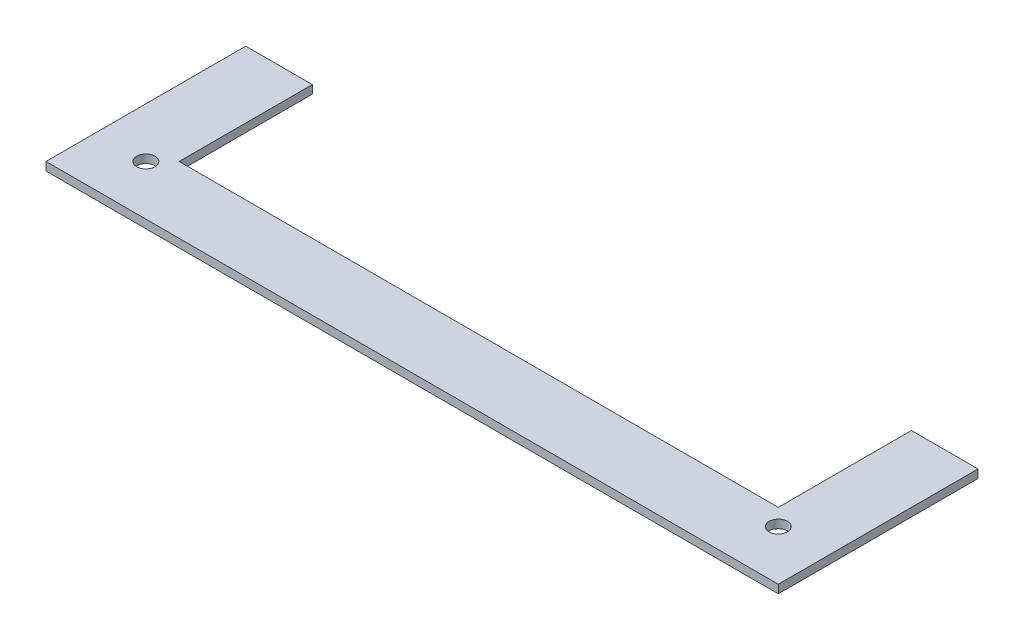
SolidWorks part; units mm, degrees
ref_plane "Front Plane" through (0, 0, 0) normal (0, 0, 1) x (1, 0, 0)
ref_plane "Top Plane" through (0, 0, 0) normal (0, 1, 0) x (1, 0, 0)
ref_plane "Right Plane" through (0, 0, 0) normal (1, 0, 0) x (0, 0, -1)
sketch "Sketch1" plane through (0, 0, 0) normal (0, 1, 0) x (1, 0, 0)
  line L0 (-139.7, 63.5) -> (-114.3, 63.5)
  line L1 (-114.3, 63.5) -> (-114.3, 12.7)
  line L2 (-114.3, 12.7) -> (114.3, 12.7)
  line L3 (114.3, 12.7) -> (114.3, 63.5)
  line L4 (114.3, 63.5) -> (139.7, 63.5)
  line L5 (139.7, 63.5) -> (139.7, -12.7)
  line L6 (139.7, -12.7) -> (-139.7, -12.7)
  line L7 (-139.7, -12.7) -> (-139.7, 63.5)
  line L8 (0, 12.7) -> (0, -12.7) construction
  line L9 (-114.3, 12.7) -> (-114.3, 6.35) construction
  line L10 (-114.3, 6.35) -> (-120.65, 6.35) construction
  line L11 (114.3, 12.7) -> (114.3, 6.35) construction
  line L12 (114.3, 6.35) -> (120.65, 6.35) construction
  circle A0 centre (-120.65, 6.35) radius 3.5
  circle A1 centre (120.65, 6.35) radius 3.5
  point P10 (0, 12.7)
  point P11 (0, -12.7)
  point P14 (0, 0)
  dimension "D5" = 7
  dimension "D1" = 279.4
  dimension "D2" = 76.2
  dimension "D3" = 25.4
  dimension "D4" = 25.4
  dimension "D6" = 6.35
extrude "Boss-Extrude1" add sketch "Sketch1" along normal blind 3.175
